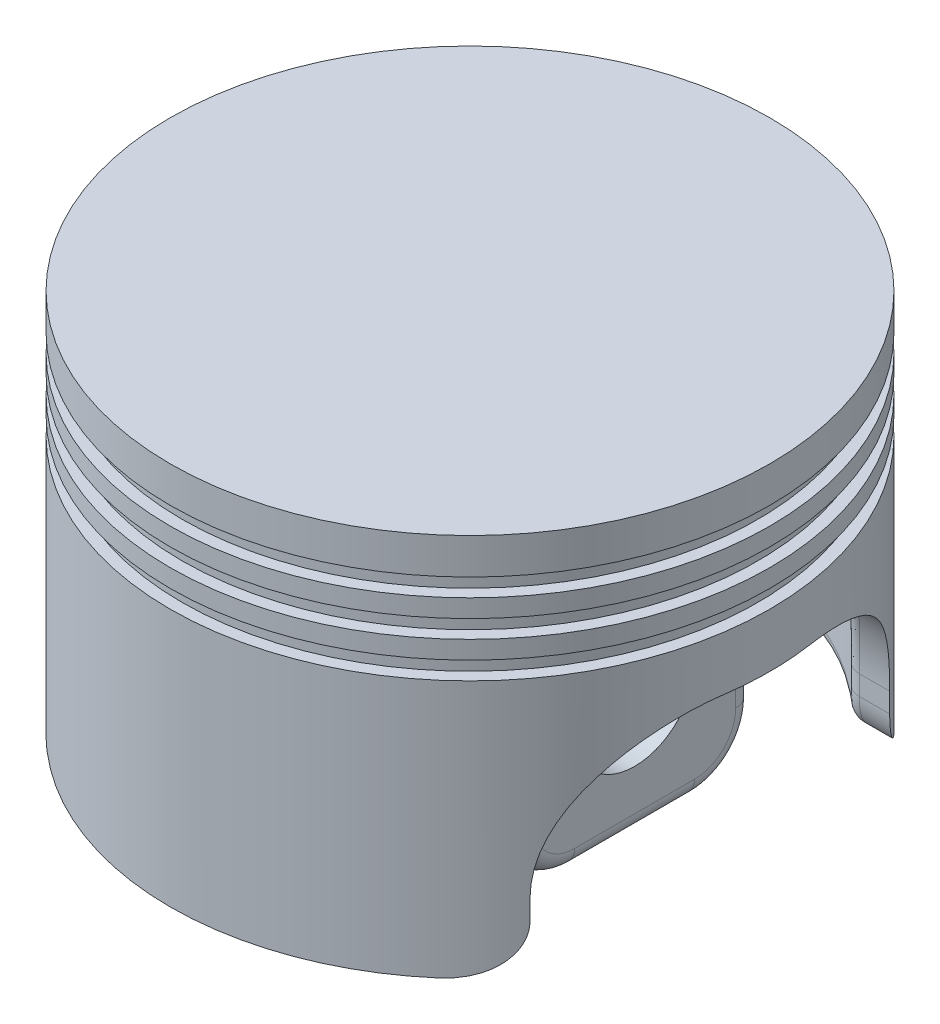
SolidWorks part; units mm, degrees
ref_plane "Front Plane" through (0, 0, 0) normal (0, 0, 1) x (1, 0, 0)
ref_plane "Top Plane" through (0, 0, 0) normal (0, 1, 0) x (1, 0, 0)
ref_plane "Right Plane" through (0, 0, 0) normal (1, 0, 0) x (0, 0, -1)
sketch "Sketch1" plane through (0, 0, 0) normal (0, 0, 1) x (1, 0, 0)
  line L0 (0, 0) -> (63.5, 0)
  line L1 (63.5, 0) -> (63.5, -81.28)
  line L2 (63.5, -81.28) -> (57.15, -81.28)
  line L3 (57.15, -81.28) -> (57.15, -19)
  line L4 (57.15, -19) -> (0, -19)
  line L5 (0, -19) -> (0, 0)
  dimension "D1" = 19
  dimension "D2" = 63.5
  dimension "D3" = 6.35
  dimension "D4" = 81.28
revolve "Revolve1" add sketch "Sketch1" angle 360 about L5
sketch "Sketch2" plane through (0, 0, 0) normal (1, 0, 0) x (0, 0, -1)
  line L0 (63.5, -81.28) -> (63.5, 0) construction
  line L1 (63.5, -7.62) -> (61, -7.62)
  line L2 (63.5, -7.62) -> (63.5, -11.42)
  line L3 (63.5, -11.42) -> (61, -11.42)
  line L4 (61, -7.62) -> (61, -11.42)
  line L5 (0, -1000) -> (0, 49000) construction
  line L6 (63.5, 0) -> (-63.5, 0) construction
  dimension "D1" = 3.8
  dimension "D2" = 2.5
  dimension "D3" = 7.62
revolve "Cut-Revolve1" cut sketch "Sketch2" angle 360 about L5
sketch "Sketch4" plane through (0, 0, 0) normal (1, 0, 0) x (0, 0, -1)
  line L0 (-57.15, -81.28) -> (57.15, -81.28) construction
  line L1 (-38.1, -38.1) -> (38.1, -38.1)
  line L2 (-38.1, -38.1) -> (-38.1, -81.28)
  line L3 (-38.1, -81.28) -> (38.1, -81.28)
  line L4 (38.1, -38.1) -> (38.1, -81.28)
  line L5 (63.5, 0) -> (-63.5, 0) construction
  point P9 (0, -38.1)
  dimension "D1" = 76.2
  dimension "D2" = 38.1
extrude "Cut-Extrude3" cut sketch "Sketch4" against normal through all both and the other way through all
pattern_linear "LPattern2" count 3 spacing 7.62 along (0, -1, 0) of "Cut-Revolve1"
fillet "Fillet1" radius 29 4 edges at (-46.6985, -38.1, 38.1) (-46.6985, -38.1, -38.1) (46.6985, -38.1, 38.1) (46.6985, -38.1, -38.1)
sketch "Sketch5" plane through (0, -19, 0) normal (0, -1, 0) x (1, 0, 0)
  line L0 (0, -1000) -> (0, 49000) construction
  line L2 (-34.88, 25.4) -> (-15.88, 25.4)
  line L3 (-34.88, 25.4) -> (-34.88, -25.4)
  line L4 (-34.88, -25.4) -> (-15.88, -25.4)
  line L5 (-15.88, 25.4) -> (-15.88, -25.4)
  point P7 (-15.88, 0)
  dimension "D1" = 19
  dimension "D2" = 50.8
  dimension "D3" = 15.88
extrude "Boss-Extrude1" add sketch "Sketch5" along normal blind 63.5
mirror "Mirror1" about plane through (0, 0, 0) normal (1, 0, 0) of "Boss-Extrude1"
sketch "Sketch6" plane through (-34.88, 0, 0) normal (-1, 0, 0) x (0, 0, 1)
  line L0 (25.4, -82.5) -> (-25.4, -82.5) construction
  circle A0 centre (0, -57.1) radius 12.7
  dimension "D1" = 25.4
  dimension "D2" = 25.4
extrude "Cut-Extrude4" cut sketch "Sketch6" against normal through all both and the other way through all
fillet "Fillet2" radius 12.7 4 edges at (25.38, -82.5, 25.4) (25.38, -82.5, -25.4) (-25.38, -82.5, 25.4) (-25.38, -82.5, -25.4)
fillet "Fillet3" radius 10 4 edges at (46.6985, -81.28, 38.1) (46.6985, -81.28, -38.1) (-46.6985, -81.28, 38.1) (-46.6985, -81.28, -38.1)
fillet "Fillet4" radius 4 14 edges at (15.88, -82.5, 0) (15.88, -78.7803, -21.6803) (15.88, -78.7803, 21.6803) (15.88, -44.4, -25.4) (15.88, -19, 0) (15.88, -44.4, 25.4) (25.38, -19, -25.4) (34.88, -19, 0) (25.38, -19, 25.4) (34.88, -44.4, -25.4) (34.88, -44.4, 25.4) (34.88, -78.7803, -21.6803) (34.88, -78.7803, 21.6803) (34.88, -82.5, 0)
fillet "Fillet5" radius 4 14 edges at (-34.88, -82.5, 0) (-34.88, -78.7803, 21.6803) (-34.88, -78.7803, -21.6803) (-34.88, -44.4, 25.4) (-34.88, -19, 0) (-34.88, -44.4, -25.4) (-25.38, -19, 25.4) (-15.88, -19, 0) (-25.38, -19, -25.4) (-15.88, -44.4, 25.4) (-15.88, -44.4, -25.4) (-15.88, -78.7803, 21.6803) (-15.88, -78.7803, -21.6803) (-15.88, -82.5, 0)
fillet "Fillet6" radius 5 1 edges at (0, -19, -57.15)
fillet "Fillet8" radius 4 16 edges at (-41.3657, -76.2692, -39.4335) (-42.5971, -69.19, -38.1) (-50.7126, -43.7888, -26.3507) (-57.15, -38.1, 0) (-46.1762, -51.7, 33.6732) (-42.5971, -69.19, 38.1) (-40.0022, -78.1316, 40.816) (0, -81.28, 57.15) (41.3657, -76.2692, 39.4335) (42.5971, -69.19, 38.1) (50.7126, -43.7888, 26.3507) (57.15, -38.1, 0) (46.1762, -51.7, -33.6732) (42.5971, -69.19, -38.1) (40.0022, -78.1316, -40.816) (0, -81.28, -57.15)
